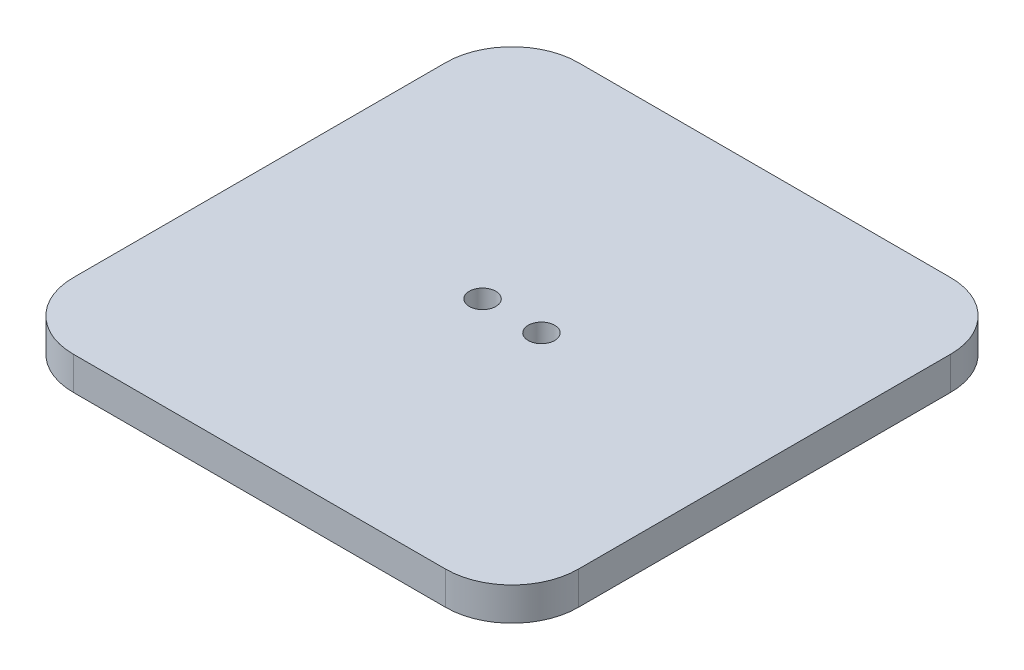
SolidWorks part; units mm, degrees
ref_plane "Front Plane" through (0, 0, 0) normal (0, 0, 1) x (1, 0, 0)
ref_plane "Top Plane" through (0, 0, 0) normal (0, 1, 0) x (1, 0, 0)
ref_plane "Right Plane" through (0, 0, 0) normal (1, 0, 0) x (0, 0, -1)
sketch "Sketch1" plane through (0, 0, 0) normal (0, 1, 0) x (1, 0, 0)
  line L1 (-38.1, -38.1) -> (38.1, -38.1)
  line L2 (-38.1, -38.1) -> (-38.1, 38.1)
  line L3 (-38.1, 38.1) -> (38.1, 38.1)
  line L4 (38.1, -38.1) -> (38.1, 38.1)
  line L5 (-38.1, -38.1) -> (38.1, 38.1) construction
  line L6 (-38.1, 38.1) -> (38.1, -38.1) construction
  point P0 (0, 0)
  dimension "D1" = 76.2
  dimension "D2" = 76.2
extrude "Boss-Extrude1" add sketch "Sketch1" along normal blind 5
fillet "Fillet1" radius 10 1 edges at (-38.1, 2.5, 38.1)
fillet "Fillet2" radius 10 1 edges at (-38.1, 2.5, -38.1)
fillet "Fillet3" radius 10 1 edges at (38.1, 2.5, -38.1)
fillet "Fillet4" radius 10 1 edges at (38.1, 2.5, 38.1)
sketch "Sketch2" plane through (0, 5, 0) normal (0, 1, 0) x (1, 0, 0)
  line L0 (-5.5, 0) -> (5.5, 0) construction
  circle A0 centre (4.445, 0) radius 2
  circle A1 centre (-4.445, 0) radius 2
  dimension "D1" = 4
  dimension "D2" = 4
  dimension "D3" = 8.89
  dimension "D4" = 4.445
extrude "Cut-Extrude1" cut sketch "Sketch2" against normal through all
ref_axis "Axis1" through (0, -0.1588, 0) along (0, 1, 0)
